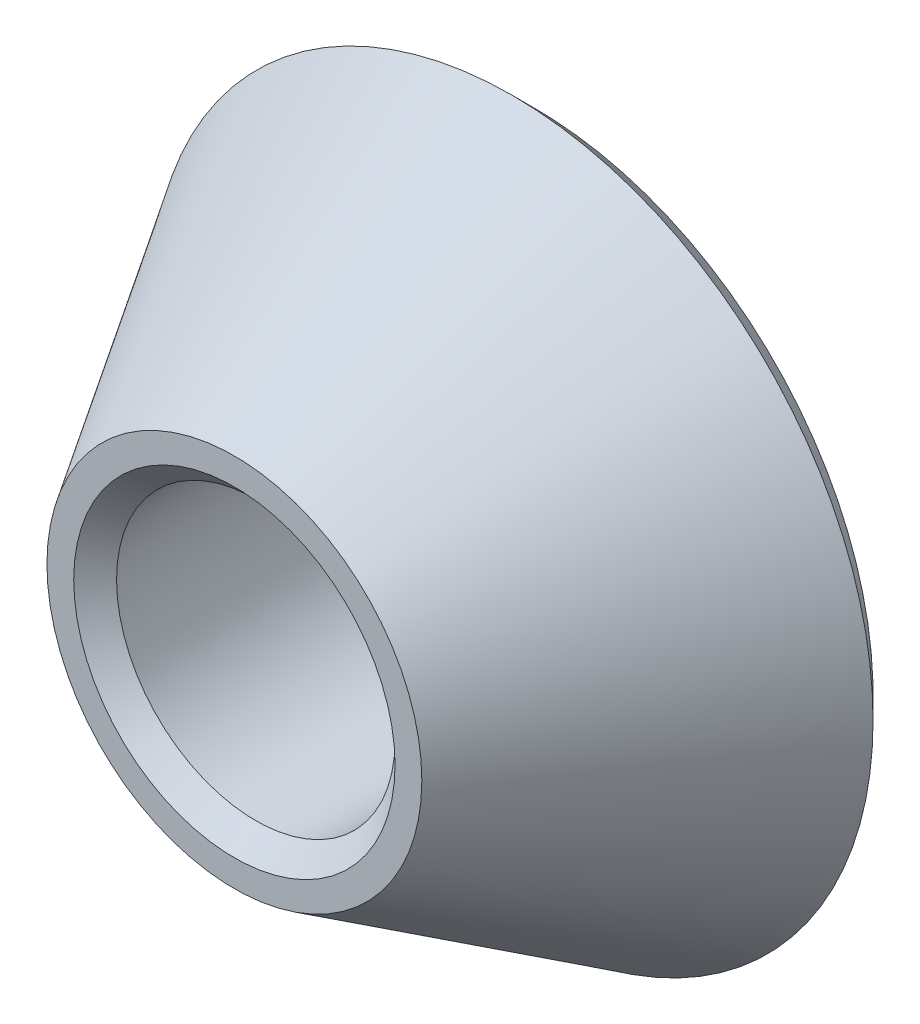
SolidWorks part; units mm, degrees
ref_plane "Front" through (0, 0, 0) normal (0, 0, 1) x (1, 0, 0)
ref_plane "Top" through (0, 0, 0) normal (0, 1, 0) x (1, 0, 0)
ref_plane "Right" through (0, 0, 0) normal (1, 0, 0) x (0, 0, -1)
sketch "Skizze5" plane through (0, 0, 0) normal (1, 0, 0) x (0, 0, -1)
  line L0 (0, 2.6) -> (-5.6, 2.6)
  line L1 (-5.6, 2.6) -> (-5.6, 3.5)
  line L2 (-5.6, 3.5) -> (-0.4151, 6.7406)
  line L3 (0, 6.3255) -> (0, 2.6)
  line L4 (0, 0) -> (-6.7737, 0) construction
  line L5 (0, 6.3255) -> (-0.4151, 6.7406)
  line L6 (0, 7) -> (0, 6.3255) construction
  line L7 (-0.4151, 6.7406) -> (0, 7) construction
  point P9 (0, 0)
  point P10 (-5.8288, 3.5)
  point P11 (0, 2.6)
  point P12 (0, 0)
  dimension "D1" = 5.6
  dimension "D2" = 5.2
  dimension "D3" = 7
  dimension "D4" = 14
  dimension "D5" = 45
revolve "Rotation1" add sketch "Skizze5" angle 360 about L4
chamfer "Fase1" distance 0.4 angle 45 2 edges at (-2.6, 0, 5.6) (-2.6, 0, 0)
